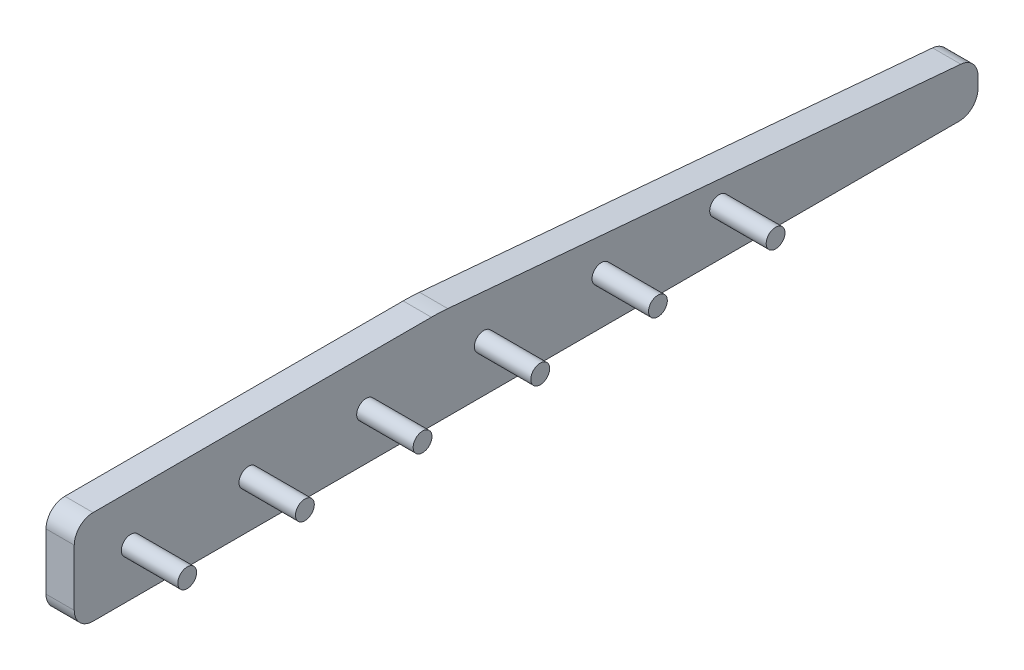
SolidWorks part; units mm, degrees
ref_plane "Front Plane" through (0, 0, 0) normal (0, 0, 1) x (1, 0, 0)
ref_plane "Top Plane" through (0, 0, 0) normal (0, 1, 0) x (1, 0, 0)
ref_plane "Right Plane" through (0, 0, 0) normal (1, 0, 0) x (0, 0, -1)
sketch "Sketch1" plane through (0, 0, 0) normal (0, 0, 1) x (1, 0, 0)
  line L0 (50.8, 0) -> (254, 0) construction
  line L1 (304.8, 50.8) -> (304.8, 121.2817) construction
  line L2 (355.6, 172.0817) -> (723.9, 172.0817) construction
  line L3 (774.7, 222.8817) -> (774.7, 375.2817) construction
  line L4 (723.9, 426.0817) -> (355.6, 426.0817) construction
  line L5 (304.8, 375.2817) -> (304.8, 355.6) construction
  line L6 (254, 304.8) -> (50.8, 304.8) construction
  line L7 (0, 254) -> (0, 50.8) construction
  line L9 (304.8, 304.8) -> (228.6, 304.8)
  line L10 (304.8, 304.8) -> (304.8, 50.8)
  line L11 (304.8, 50.8) -> (228.6, 50.8)
  line L12 (228.6, 304.8) -> (228.6, 50.8)
  arc A0 (355.6, 426.0817) -> (304.8, 375.2817) centre (355.6, 375.2817) ccw construction
  arc A1 (774.7, 375.2817) -> (723.9, 426.0817) centre (723.9, 375.2817) ccw construction
  arc A2 (723.9, 172.0817) -> (774.7, 222.8817) centre (723.9, 222.8817) ccw construction
  arc A3 (254, 0) -> (304.8, 50.8) centre (254, 50.8) ccw construction
  arc A4 (50.8, 0) -> (0, 50.8) centre (50.8, 50.8) cw construction
  arc A5 (304.8, 121.2817) -> (355.6, 172.0817) centre (355.6, 121.2817) cw construction
  arc A6 (50.8, 304.8) -> (0, 254) centre (50.8, 254) ccw construction
  arc A7 (304.8, 355.6) -> (254, 304.8) centre (254, 355.6) cw construction
  point P11 (304.8, 426.0817)
  point P14 (774.7, 426.0817)
  point P17 (774.7, 172.0817)
  point P20 (304.8, 0)
  point P23 (0, 0)
  point P26 (304.8, 172.0817)
  point P29 (0, 304.8)
  point P32 (304.8, 304.8)
  point P37 (0, 0)
  dimension "D5" = 50.8
  dimension "D1" = 304.8
  dimension "D2" = 304.8
  dimension "D3" = 469.9
  dimension "D4" = 254
  dimension "D6" = 0
  dimension "D7" = 76.2
extrude "Boss-Extrude1" add sketch "Sketch1" along normal blind 2438.4
sketch "Sketch2" plane through (304.8, 0, 0) normal (1, 0, 0) x (0, 0, -1)
  line L0 (0, 177.8) -> (-1452.626, 304.8)
  line L1 (0, 50.8) -> (0, 304.8) construction
  line L2 (-2438.4, 304.8) -> (0, 304.8) construction
  line L3 (-1452.626, 304.8) -> (0, 304.8)
  line L4 (0, 304.8) -> (0, 177.8)
  dimension "D1" = 1452.626
extrude "Cut-Extrude1" cut sketch "Sketch2" against normal through all
fillet "Fillet1" radius 50.8 4 edges at (266.7, 304.8, 2438.4) (266.7, 50.8, 2438.4) (266.7, 50.8, 0) (266.7, 177.8, 0)
fillet "Fillet2" radius 508 1 edges at (266.7, 304.8, 1452.626)
sketch "Sketch3" plane through (304.8, 0, 0) normal (1, 0, 0) x (0, 0, -1)
  line L0 (-2438.4, 101.6) -> (-2438.4, 254) construction
  circle A0 centre (-2286, 177.8) radius 25.4
  point P6 (-2438.4, 177.8)
  dimension "D1" = 50.8
  dimension "D2" = 152.4
extrude "Boss-Extrude2" add sketch "Sketch3" along normal blind 152.4
pattern_linear "LPattern1" count 6 spacing 317.5 along (0, 0, -1) of "Boss-Extrude2"
ref_plane "Plane1" through (266.7, 0, 0) normal (1, 0, 0) x (0, 0, -1)
